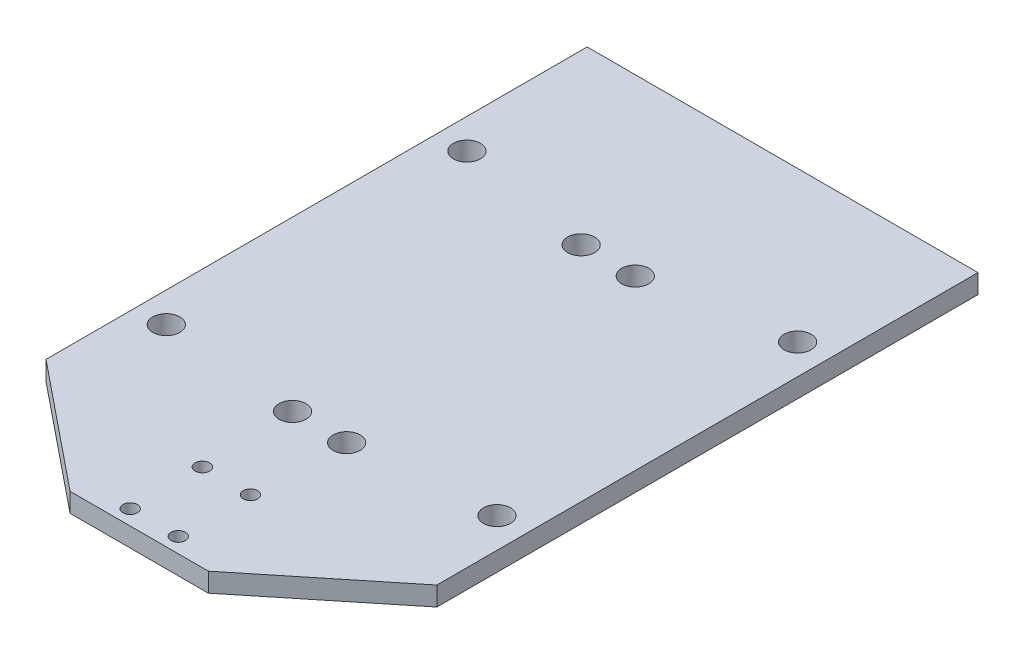
SolidWorks part; units mm, degrees
material "6061-T6 (SS)"
ref_plane "Front Plane" through (0, 0, 0) normal (0, 0, 1) x (1, 0, 0)
ref_plane "Top Plane" through (0, 0, 0) normal (0, 1, 0) x (1, 0, 0)
ref_plane "Right Plane" through (0, 0, 0) normal (1, 0, 0) x (0, 0, -1)
sketch "Sketch1" plane through (0, 0, 0) normal (0, 1, 0) x (1, 0, 0)
  line L0 (-11.5, -62) -> (-32.5, -45)
  line L1 (32.5, -45) -> (-32.5, -45)
  line L2 (32.5, -45) -> (32.5, 45)
  line L3 (32.5, 45) -> (-32.5, 45)
  line L4 (-32.5, -45) -> (-32.5, 45)
  line L5 (32.5, -45) -> (-32.5, 45) construction
  line L6 (32.5, 45) -> (-32.5, -45) construction
  line L7 (-11.5, -45) -> (11.5, -45)
  line L8 (-11.5, -45) -> (-11.5, -62)
  line L9 (-11.5, -62) -> (11.5, -62)
  line L10 (11.5, -45) -> (11.5, -62)
  line L11 (11.5, -62) -> (32.5, -45)
  line L12 (-32.5, -45) -> (32.5, -45)
  line L13 (11.5, -62) -> (-11.5, -62)
  point P0 (0, 0)
  point P10 (0, -62)
  dimension "D1" = 90
  dimension "D2" = 65
  dimension "D3" = 23
  dimension "D4" = 17
  dimension "D5" = 32.5
extrude "Boss-Extrude1" add sketch "Sketch1" along normal mid plane 3.175 contours L8 L1 L0 | L10 L11 L1 | L4 L1 L2 L3 | L10 L1 L8 L9 region at (-18.5, 0, 50.6667) region at (0, 0, 53.5) region at (0, 0, 0) region at (18.5, 0, 50.6667)
sketch "Sketch4" plane through (0, 1.5875, 0) normal (0, 1, 0) x (1, 0, 0)
  line L0 (-11.5, -62) -> (11.5, -62) construction
  point P0 (-4, -59.5)
  point P2 (4, -59.5)
  point P4 (4, -47.5)
  point P6 (-4, -47.5)
  point P16 (0, -62)
  dimension "D1" = 8
  dimension "D2" = 12
  dimension "D3" = 4
  dimension "D4" = 2.5
hole_wizard "M2 Clearance Hole1" positions "Sketch4" profile "Sketch3" hole size "M2" standard "ANSI Metric" end condition through all
sketch "Sketch3" plane through (-4, 1.5875, 59.5) normal (1, 0, 0) x (0, 0, 1)
  line L0 (0, 0) -> (0, 3.175)
  line L1 (0, 3.175) -> (1.2, 3.175)
  line L2 (1.2, 3.175) -> (1.2, 0)
  line L5 (1.2, 0) -> (0, 0)
  line L11 (0, -6.35) -> (0, 107.95) construction
  dimension "Thru Hole Dia." = 2.4
  dimension "Thru Hole Depth" = 3.175
sketch "Sketch7" plane through (0, 1.5875, 0) normal (0, 1, 0) x (1, 0, 0)
  line L0 (-32.5, -45) -> (-32.5, 45) construction
  line L1 (32.5, -45) -> (32.5, 45) construction
  line L2 (32.5, 45) -> (-32.5, 45) construction
  point P0 (-27.5, 20)
  point P2 (27.5, 20)
  point P4 (27.5, -30)
  point P6 (-27.5, -30)
  dimension "D1" = 5
  dimension "D2" = 5
  dimension "D3" = 25
  dimension "D4" = 50
hole_wizard "M4 Clearance Hole1" positions "Sketch7" profile "Sketch6" hole size "M4" standard "ANSI Metric" end condition through all
sketch "Sketch6" plane through (-27.5, 1.5875, -20) normal (1, 0, 0) x (0, 0, 1)
  line L0 (0, 0) -> (0, 3.175)
  line L1 (0, 3.175) -> (2.25, 3.175)
  line L2 (2.25, 3.175) -> (2.25, 0)
  line L5 (2.25, 0) -> (0, 0)
  line L11 (0, -6.35) -> (0, 107.95) construction
  dimension "Thru Hole Dia." = 4.5
  dimension "Thru Hole Depth" = 3.175
hole_wizard "M4 Clearance Hole2" positions "Sketch12" profile "Sketch9" hole size "M4" standard "ANSI Metric" end condition through all
sketch "Sketch12" plane through (0, 1.5875, 0) normal (0, 1, 0) x (1, 0, 0)
  line L0 (-11.5, -62) -> (11.5, -62) construction
  point P0 (-4.5, -32)
  point P2 (4.5, -32)
  point P4 (4.5, 16)
  point P6 (-4.5, 16)
  point P17 (0, -62)
  dimension "D1" = 48
  dimension "D2" = 9
  dimension "D3" = 4.5
  dimension "D4" = 30
sketch "Sketch9" plane through (-4.5, 1.5875, 32) normal (1, 0, 0) x (0, 0, 1)
  line L0 (0, 0) -> (0, 3.175)
  line L1 (0, 3.175) -> (2.25, 3.175)
  line L2 (2.25, 3.175) -> (2.25, 0)
  line L5 (2.25, 0) -> (0, 0)
  line L11 (0, -6.35) -> (0, 107.95) construction
  dimension "Thru Hole Dia." = 4.5
  dimension "Thru Hole Depth" = 3.175
